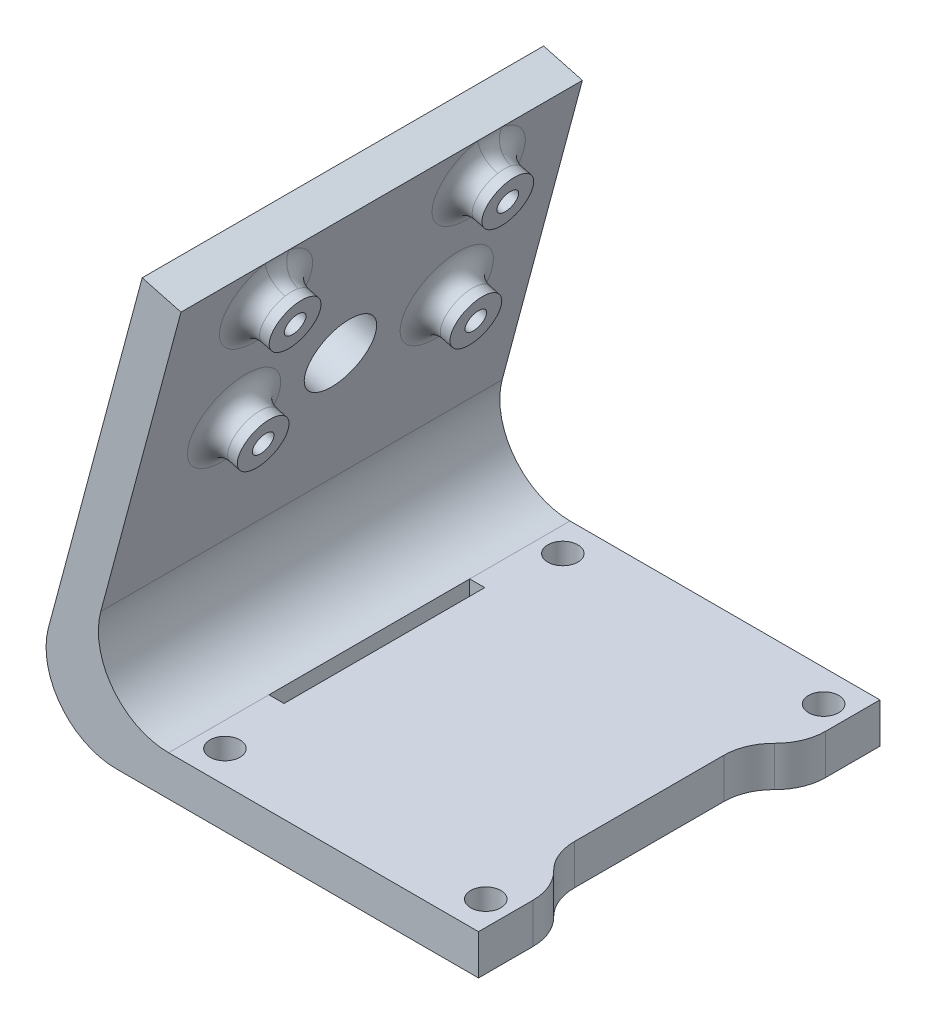
SolidWorks part; units mm, degrees
ref_plane "Piano frontale" through (0, 0, 0) normal (0, 0, 1) x (1, 0, 0)
ref_plane "Piano superiore" through (0, 0, 0) normal (0, 1, 0) x (1, 0, 0)
ref_plane "Piano destro" through (0, 0, 0) normal (1, 0, 0) x (0, 0, -1)
sketch "Schizzo1" plane through (0, 0, 0) normal (0, 0, 1) x (1, 0, 0)
  line L0 (0, 0) -> (-40, 0)
  line L5 (-40, 0) -> (-29.6472, 38.637)
  line L6 (0, -4) -> (-45.2129, -4)
  line L7 (-45.2129, -4) -> (-33.5109, 39.6723)
  line L8 (-33.5109, 39.6723) -> (-29.6472, 38.637)
  line L9 (0, 0) -> (0, -4)
  dimension "D1" = 75
  dimension "D2" = 40
  dimension "D3" = 40
  dimension "D4" = 4
extrude "Estrusione-Estrusione1" add sketch "Schizzo1" along normal blind 40
fillet "Raccordo1" radius 7 2 edges at (-40, 0, 20) (-45.2129, -4, 20)
sketch "Schizzo2" plane through (0, 0, 0) normal (0, 1, 0) x (1, 0, 0)
  line L0 (-30.8774, 0) -> (-30.8774, -40) construction
  line L1 (-30.8774, -10) -> (-29.3774, -10)
  line L2 (-30.8774, -10) -> (-30.8774, -30)
  line L3 (-30.8774, -30) -> (-29.3774, -30)
  line L4 (-29.3774, -10) -> (-29.3774, -30)
  line L5 (0, -40) -> (-30.8774, -40) construction
  dimension "D1" = 20
  dimension "D2" = 10
  dimension "D3" = 1.5
extrude "Taglio-Estrusione1" cut sketch "Schizzo2" against normal blind 40
sketch "Schizzo3" plane through (-41.1842, 11.0353, 0) normal (-0.9659, 0.2588, 0) x (0, 0, 1)
  line L7 (7.2057, 3.2171) -> (32.4057, 27.2171) construction
  line L8 (7.2057, 27.2171) -> (32.4057, 3.2171) construction
  line L10 (19.8057, 15.2171) -> (19.8057, 27.2171) construction
  line L11 (30.4029, 25.3096) -> (30.4029, 13.0096) construction
  line L12 (30.4029, 25.3096) -> (19.9029, 13.4096) construction
  line L13 (30.4029, 25.3096) -> (9.2086, 25.3096) construction
  circle A1 centre (30.4029, 25.3096) radius 1.05
  circle A2 centre (9.2086, 25.3096) radius 1.05
  circle A3 centre (30.4029, 13.0096) radius 1.05
  circle A4 centre (9.2086, 13.0096) radius 1.05
  circle A6 centre (19.9029, 13.4096) radius 3.5
  point P8 (19.8057, 15.2171)
  point P13 (30.4029, 25.3096)
  point P24 (18.9107, 14.3647)
  dimension "D5" = 2.7659
  dimension "D6" = 2.1
  dimension "D8" = 2.1
  dimension "D11" = 7
  dimension "D1" = 24
  dimension "D2" = 25.2
  dimension "D7" = 12.3
  dimension "D9" = 15.8701
  dimension "D10" = 48.576
extrude "Taglio-Estrusione2" cut sketch "Schizzo3" against normal blind 40
sketch "Schizzo4" plane through (-37.3205, 10, 0) normal (0.9659, -0.2588, 0) x (0, 0, -1)
  circle A0 centre (-9.2086, 13.0096) radius 2.5
  circle A1 centre (-30.4029, 13.0096) radius 2.5
  circle A2 centre (-30.4029, 25.3096) radius 2.5
  circle A3 centre (-9.2086, 25.3096) radius 2.5
  circle A4 centre (-9.2086, 13.0096) radius 1.05
  circle A5 centre (-30.4029, 13.0096) radius 1.05
  circle A6 centre (-30.4029, 25.3096) radius 1.05
  circle A7 centre (-9.2086, 25.3096) radius 1.05
  dimension "D1" = 5
  dimension "D2" = 5
  dimension "D3" = 5
  dimension "D4" = 5
extrude "Estrusione-Estrusione2" add sketch "Schizzo4" along normal blind 3
fillet "Raccordo2" radius 2 4 edges at (-31.417, 32.0324, 30.4029) (-31.417, 32.0324, 9.2086) (-34.6004, 20.1515, 30.4029) (-34.6004, 20.1515, 9.2086)
sketch "Schizzo5" plane through (0, 0, 0) normal (0, 1, 0) x (1, 0, 0)
  line L0 (0, 0) -> (-30.8774, -40) construction
  line L1 (0, -40) -> (-30.8774, 0) construction
  circle A0 centre (-2.4442, -36.8336) radius 1.5
  circle A1 centre (-2.4442, -3.1664) radius 1.5
  circle A2 centre (-28.4332, -3.1664) radius 1.5
  circle A3 centre (-28.4332, -36.8336) radius 1.5
  dimension "D1" = 3
  dimension "D2" = 3
  dimension "D3" = 3
  dimension "D4" = 3
  dimension "D5" = 4
  dimension "D6" = 4
  dimension "D7" = 4
  dimension "D8" = 4
extrude "Taglio-Estrusione3" cut sketch "Schizzo5" against normal blind 17
sketch "Schizzo6" plane through (0, 0, 0) normal (0, 1, 0) x (1, 0, 0)
  line L0 (0, -40) -> (0, 0) construction
  line L1 (0, -20) -> (0, -30)
  line L2 (0, -20) -> (0, -10)
  line L3 (0, -30) -> (-3, -30)
  line L4 (0, -10) -> (-3, -10)
  line L5 (-3, -10) -> (-3, -30)
  dimension "D1" = 10
  dimension "D2" = 10
  dimension "D3" = 3
extrude "Taglio-Estrusione4" cut sketch "Schizzo6" against normal blind 10
fillet "Raccordo3" radius 5 2 edges at (0, -2, 10) (0, -2, 30)
fillet "Raccordo4" radius 5 2 edges at (-3, -2, 10) (-3, -2, 30)
